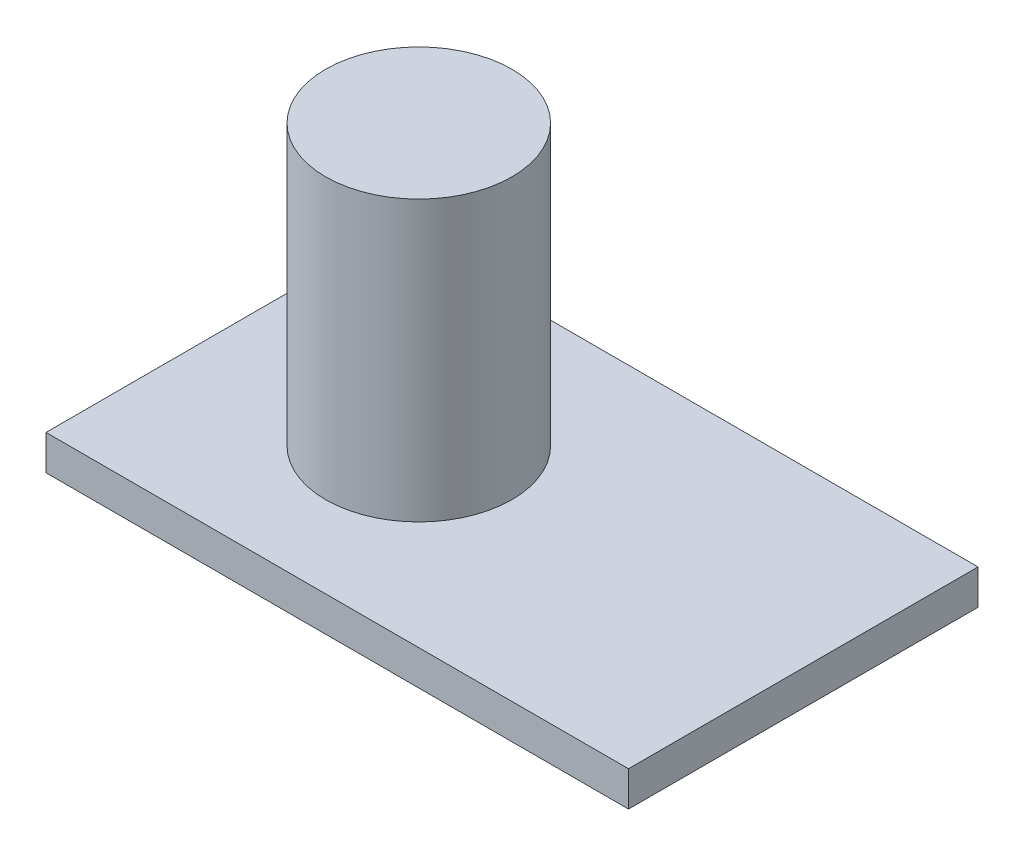
SolidWorks part; units mm, degrees
ref_plane "Front Plane" through (0, 0, 0) normal (0, 0, 1) x (1, 0, 0)
ref_plane "Top Plane" through (0, 0, 0) normal (0, 1, 0) x (1, 0, 0)
ref_plane "Right Plane" through (0, 0, 0) normal (1, 0, 0) x (0, 0, -1)
other "Configuration Table"
sketch "Sketch1" plane through (0, 0, 0) normal (0, 1, 0) x (1, 0, 0)
  line L1 (-1250, -750) -> (1250, -750)
  line L2 (-1250, -750) -> (-1250, 750)
  line L3 (-1250, 750) -> (1250, 750)
  line L4 (1250, -750) -> (1250, 750)
extrude "Boss-Extrude1" add sketch "Sketch1" against normal blind 150 flip side to cut separate body
sketch "Sketch2" plane through (0, 0, 0) normal (0, 1, 0) x (1, 0, 0)
  circle A0 centre (-400, 0) radius 400
extrude "Boss-Extrude2" add sketch "Sketch2" along normal blind 1200 separate body
